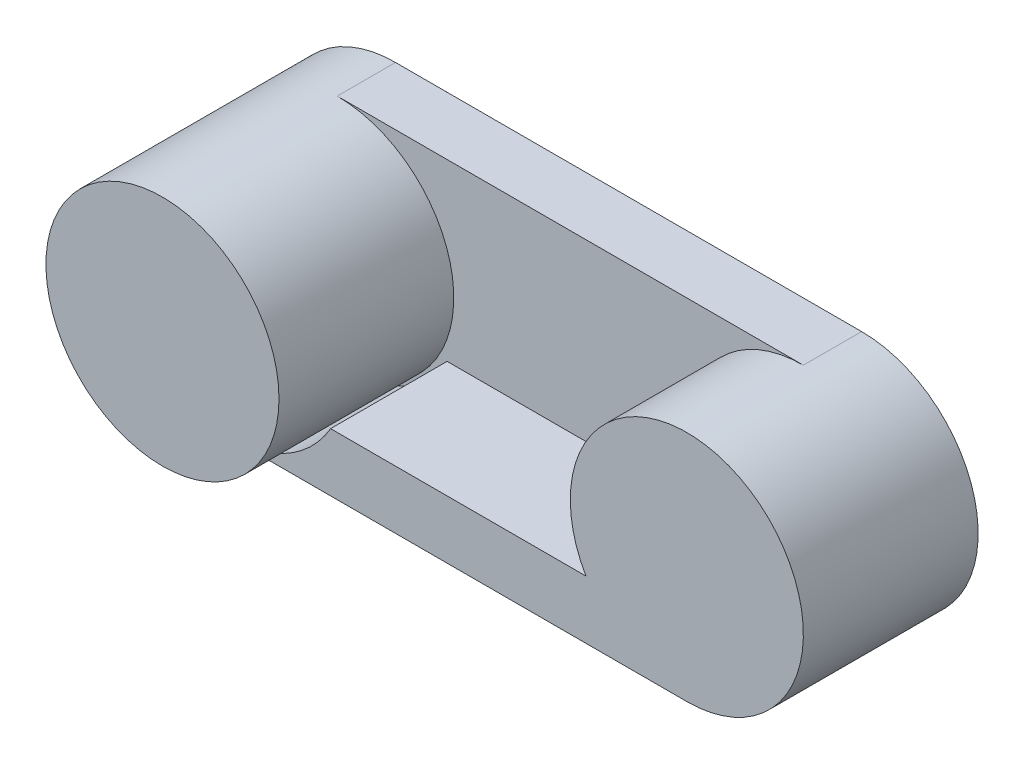
SolidWorks part; units mm, degrees
ref_plane "Front Plane" through (0, 0, 0) normal (0, 0, 1) x (1, 0, 0)
ref_plane "Top Plane" through (0, 0, 0) normal (0, 1, 0) x (1, 0, 0)
ref_plane "Right Plane" through (0, 0, 0) normal (1, 0, 0) x (0, 0, -1)
sketch "Sketch1" plane through (0, 0, 0) normal (0, 0, 1) x (1, 0, 0)
  line L0 (-49.3886, 20) -> (30.6114, 20)
  line L1 (30.6114, -20) -> (-49.3886, -20)
  line L2 (-49.3886, 0) -> (-49.3886, 51.9177) construction
  line L3 (30.6114, 0) -> (30.6114, 47.8661) construction
  arc A0 (-49.3886, 20) -> (-49.3886, -20) centre (-49.3886, 0) ccw
  arc A1 (30.6114, -20) -> (30.6114, 20) centre (30.6114, 0) ccw
  dimension "D2" = 40
  dimension "D1" = 80
extrude "Boss-Extrude2" add sketch "Sketch1" along normal blind 10
sketch "Sketch3" plane through (0, 0, 10) normal (0, 0, 1) x (1, 0, 0)
  circle A0 centre (-49.3886, 0) radius 20
  dimension "D1" = 40
extrude "Boss-Extrude3" add sketch "Sketch3" along normal blind 30
sketch "Sketch4" plane through (0, 0, 10) normal (0, 0, 1) x (1, 0, 0)
  line L0 (30.6114, -20) -> (-47.8527, -20)
  line L1 (-30.5322, -10) -> (13.2909, -10)
  arc A0 (30.6114, -20) -> (13.2909, -10) centre (30.6114, 0) ccw
  arc A1 (-47.8527, -20) -> (-30.5322, -10) centre (-47.8527, 0) ccw
  point P1 (-197.6263, 2.7746)
  dimension "D2" = 40
  dimension "D3" = 10
extrude "Boss-Extrude5" add sketch "Sketch4" along normal blind 20 separate body
combine bodies "Combine4" operation type add bodies to combine 103 105
